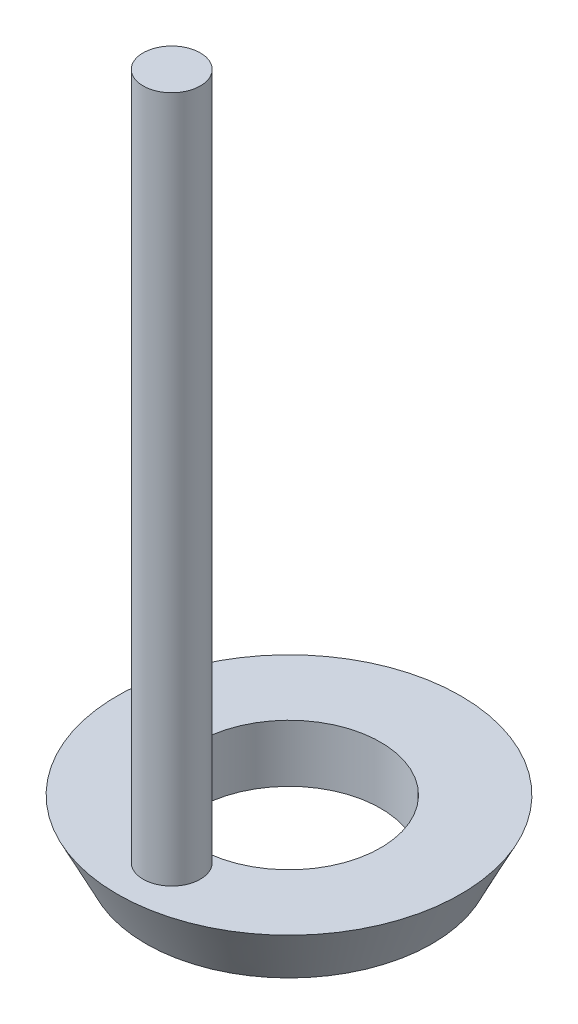
SolidWorks part; units mm, degrees
ref_plane "Front Plane" through (0, 0, 0) normal (0, 0, 1) x (1, 0, 0)
ref_plane "Top Plane" through (0, 0, 0) normal (0, 1, 0) x (1, 0, 0)
ref_plane "Right Plane" through (0, 0, 0) normal (1, 0, 0) x (0, 0, -1)
sketch "Sketch1" plane through (0, 0, 0) normal (0, 1, 0) x (1, 0, 0)
  circle A0 centre (0, 0) radius 3
extrude "Boss-Extrude1" add sketch "Sketch1" along normal blind 1
sketch "Sketch2" plane through (0, 1, 0) normal (0, 1, 0) x (1, 0, 0)
  circle A0 centre (0, 0) radius 1.6
extrude "Cut-Extrude1" cut sketch "Sketch2" against normal blind 1
sketch "Sketch3" plane through (0, 1, 0) normal (0, 1, 0) x (1, 0, 0)
  circle A0 centre (0, -2.0484) radius 0.5
extrude "Boss-Extrude2" add sketch "Sketch3" along normal blind 12
chamfer "Chamfer1" distance 0.5 distance2 1 1 edges at (0, 0, 3) first distance on face at (0, 0, 1.6)
